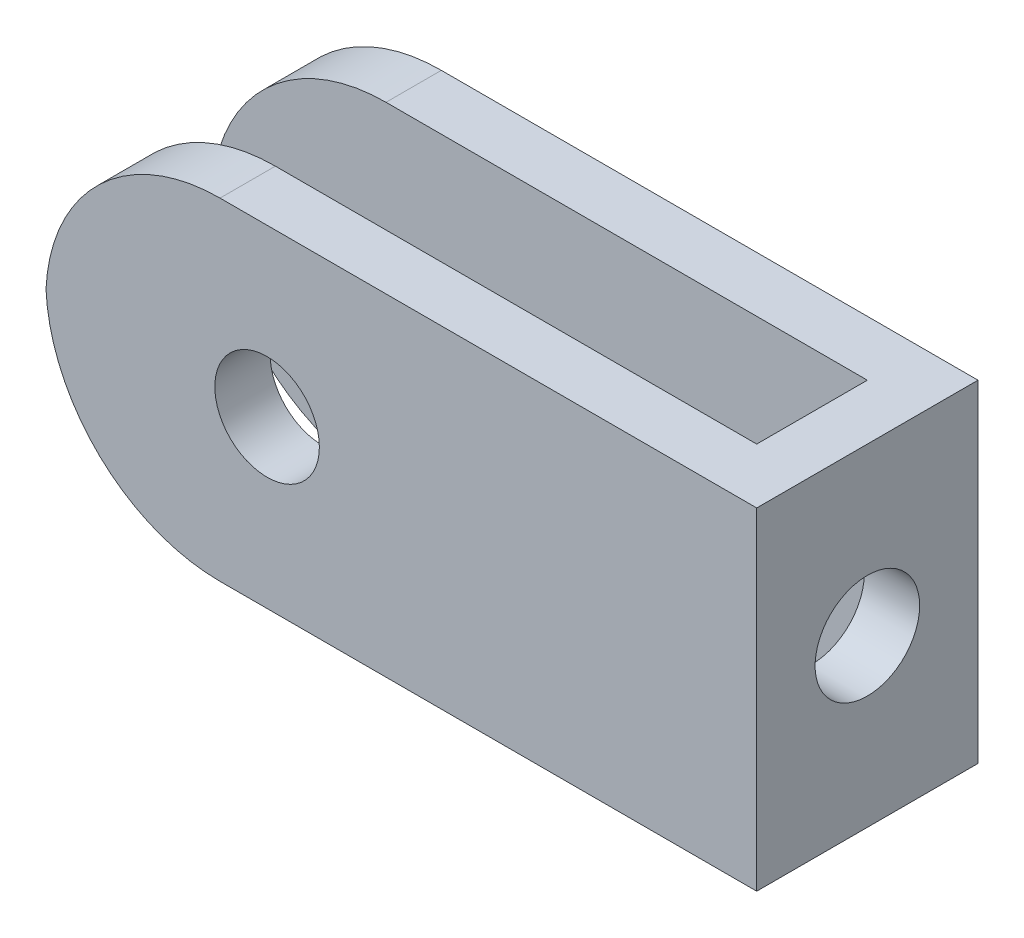
SolidWorks part; units mm, degrees
ref_plane "Front Plane" through (0, 0, 0) normal (0, 0, 1) x (1, 0, 0)
ref_plane "Top Plane" through (0, 0, 0) normal (0, 1, 0) x (1, 0, 0)
ref_plane "Right Plane" through (0, 0, 0) normal (1, 0, 0) x (0, 0, -1)
sketch "Sketch1" plane through (0, 0, 0) normal (0, 1, 0) x (1, 0, 0)
  line L0 (0, 0) -> (37.625, 0)
  line L1 (37.625, 0) -> (37.625, -6.35)
  line L2 (37.625, -6.35) -> (0, -6.35)
  line L3 (0, 3.175) -> (40.8, 3.175)
  line L4 (40.8, 3.175) -> (40.8, -9.525)
  line L5 (40.8, -9.525) -> (0, -9.525)
  line L6 (0, 3.175) -> (0, 0)
  line L7 (0, -6.35) -> (0, -9.525)
  point P9 (0, 1.5875)
  dimension "D2" = 6.35
  dimension "D4" = 40.8
  dimension "D1" = 3.175
extrude "Boss-Extrude1" add sketch "Sketch1" along normal blind 19.05
sketch "Sketch2" plane through (40.8, 0, 0) normal (1, 0, 0) x (0, 0, -1)
  line L0 (-3.175, 19.05) -> (-3.175, 0) construction
  line L1 (-9.525, 19.05) -> (3.175, 19.05) construction
  line L2 (-9.525, 0) -> (3.175, 0) construction
  line L3 (3.175, 9.525) -> (-9.525, 9.525) construction
  line L4 (3.175, 19.05) -> (3.175, 0) construction
  line L5 (-9.525, 19.05) -> (-9.525, 0) construction
  circle A0 centre (-3.175, 9.525) radius 3
  dimension "D1" = 6
extrude "Cut-Extrude1" cut sketch "Sketch2" against normal up to surface (3.175 mm away) up to face at (37.625, 9.525, 3.175)
sketch "Sketch3" plane through (0, 0, 9.525) normal (0, 0, 1) x (1, 0, 0)
  line L1 (0, 19.05) -> (0, 0) construction
  line L2 (0, 9.525) -> (40.8, 9.525) construction
  line L3 (40.8, 19.05) -> (40.8, 0) construction
  circle A0 centre (12.7, 9.525) radius 3
  dimension "D1" = 6
  dimension "D3" = 12.7
extrude "Cut-Extrude2" cut sketch "Sketch3" against normal up to surface (12.7 mm away) up to face at (20.4, 9.525, -3.175)
fillet "Fillet1" radius 10 4 edges at (0, 0, -1.5875) (0, 19.05, -1.5875) (0, 0, 7.9375) (0, 19.05, 7.9375)
